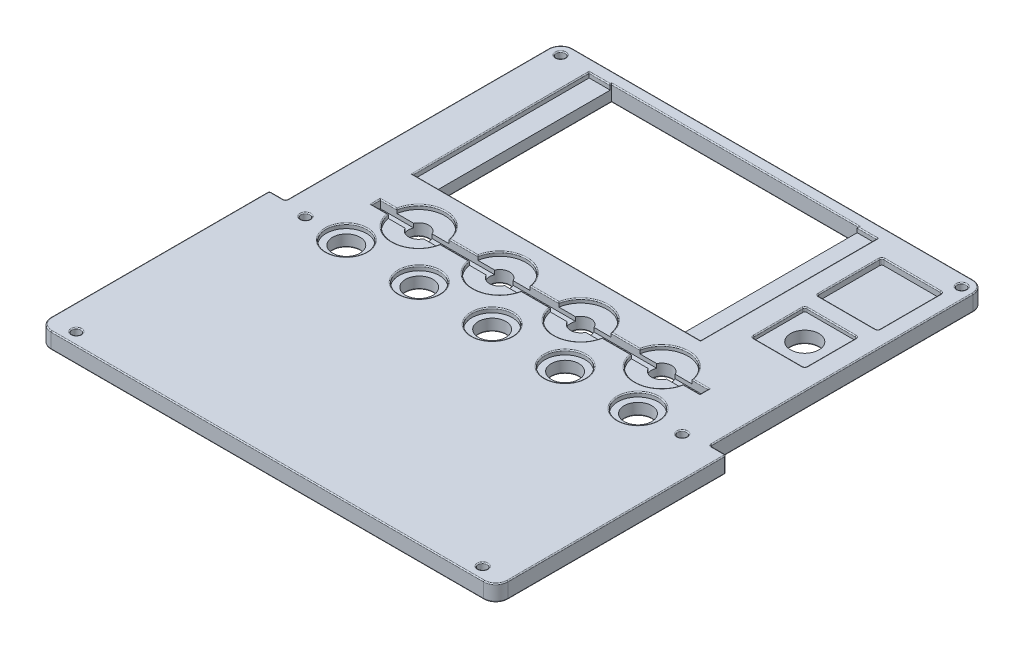
SolidWorks part; units mm, degrees
ref_plane "Front Plane" through (0, 0, 0) normal (0, 0, 1) x (1, 0, 0)
ref_plane "Top Plane" through (0, 0, 0) normal (0, 1, 0) x (1, 0, 0)
ref_plane "Right Plane" through (0, 0, 0) normal (1, 0, 0) x (0, 0, -1)
sketch "Sketch1" plane through (0, 0, 0) normal (0, 1, 0) x (1, 0, 0)
  line L0 (112.8, 56.9) -> (108.8, 56.9)
  line L1 (0, 0) -> (112.8, 0)
  line L2 (0, 0) -> (0, 56.9)
  line L3 (0, 56.9) -> (112.8, 56.9) construction
  line L4 (112.8, 0) -> (112.8, 56.9)
  line L5 (4, 56.9) -> (0, 56.9)
  line L6 (4, 56.9) -> (4, 124.8)
  line L7 (4, 124.8) -> (108.8, 124.8)
  line L8 (108.8, 56.9) -> (108.8, 124.8)
  line L9 (0, 56.9) -> (112.8, 56.9) construction
  dimension "D1" = 104.8
  dimension "D2" = 112.8
  dimension "D3" = 67.9
  dimension "D4" = 56.9
extrude "Main" add sketch "Sketch1" along normal blind 4
sketch "Outline Display" plane through (0, 0, 0) normal (0, -1, 0) x (1, 0, 0)
  line L0 (4, -124.8) -> (4, -81.05) construction
  line L1 (4, -124.8) -> (4, -56.9) construction
  line L2 (4, -81.05) -> (17, -81.05) construction
  line L3 (17, -81.05) -> (17, -78.32) construction
  line L4 (14.23, -78.32) -> (85.03, -78.32) construction
  line L5 (14.23, -78.32) -> (14.23, -121.62) construction
  line L6 (14.23, -121.62) -> (85.03, -121.62) construction
  line L7 (85.03, -78.32) -> (85.03, -121.62) construction
  line L8 (17, -81.05) -> (14.23, -81.05) construction
  point P7 (17, -81.05)
  dimension "D1" = 43.75
  dimension "D2" = 13
  dimension "D3" = 2.73
  dimension "D4" = 2.77
  dimension "D5" = 43.3
  dimension "D6" = 70.8
sketch "Display PCB Notch" plane through (0, 4, 0) normal (0, -1, 0) x (1, 0, 0)
  line L0 (14.23, -78.32) -> (14.23, -78.22) construction
  line L1 (14.13, -78.22) -> (85.13, -78.22)
  line L2 (14.13, -78.22) -> (14.13, -121.72)
  line L3 (14.13, -121.72) -> (85.13, -121.72)
  line L4 (85.13, -78.22) -> (85.13, -121.72)
  line L5 (14.23, -78.32) -> (14.13, -78.32) construction
  line L6 (85.03, -121.62) -> (85.03, -121.72) construction
  line L7 (85.03, -121.62) -> (85.13, -121.62) construction
  dimension "D2" = 0.1
extrude "PCB Notch" cut sketch "Display PCB Notch" along normal blind 1.2
sketch "Sketch4" plane through (0, 0, 0) normal (0, -1, 0) x (-1, 0, 0)
  line L0 (-14.23, 78.32) -> (-85.03, 78.32) construction
  line L1 (-19.33, 78.87) -> (-80.29, 78.87)
  line L2 (-19.33, 78.87) -> (-19.33, 122.05)
  line L3 (-19.33, 122.05) -> (-80.29, 122.05)
  line L4 (-80.29, 78.87) -> (-80.29, 122.05)
  dimension "D1" = 5.1
  dimension "D2" = 0.55
  dimension "D3" = 60.96
  dimension "D4" = 43.18
extrude "Display Cut" cut sketch "Sketch4" against normal up to next
sketch "Sketch5" plane through (0, 0, 0) normal (0, -1, 0) x (1, 0, 0)
  line L0 (108.8, -56.9) -> (108.8, -124.8) construction
  line L1 (89.12, -102.2) -> (97.32, -102.2) construction
  line L2 (97.32, -102.2) -> (97.32, -91.75) construction
  circle A0 centre (97.32, -91.75) radius 3.5
  point P0 (89.12, -102.2)
  point P1 (108.8, -124.8)
  point P9 (97.32, -91.75)
  dimension "D5" = 7
  dimension "D1" = 22.6
  dimension "D2" = 19.68
  dimension "D3" = 10.45
  dimension "D4" = 8.2
extrude "Rotary Hole" cut sketch "Sketch5" against normal up to next
sketch "Sketch6" plane through (0, 0, 0) normal (0, -1, 0) x (1, 0, 0)
  line L0 (6.9, -124.8) -> (6.9, -121.9) construction
  line L1 (108.8, -124.8) -> (4, -124.8) construction
  line L2 (6.9, -121.9) -> (4, -121.9) construction
  line L3 (4, -124.8) -> (4, -56.9) construction
  line L4 (56.4, 0) -> (56.4, -124.8) construction
  line L5 (0, 0) -> (112.8, 0) construction
  line L6 (0, -55.9) -> (9.9, -55.9) construction
  line L7 (0, -56.9) -> (0, 0) construction
  line L8 (4, -56.9) -> (0, -56.9) construction
  line L9 (0, -3) -> (6.25, -3) construction
  circle A0 centre (6.9, -121.9) radius 1.1
  circle A1 centre (9.9, -55.9) radius 1.1
  circle A2 centre (6.25, -3) radius 1.1
  circle A3 centre (105.9, -121.9) radius 1.1
  circle A4 centre (102.9, -55.9) radius 1.1
  circle A5 centre (106.55, -3) radius 1.1
  dimension "D1" = 2.2
  dimension "D7" = 6.25
  dimension "D2" = 2.9
  dimension "D3" = 2.9
  dimension "D4" = 9.9
  dimension "D5" = 1
  dimension "D6" = 3
extrude "Mounts" cut sketch "Sketch6" against normal up to next contours A0 | A1 | A2 | A5 | A4 | A3
fillet "Fillet1" radius 3 4 edges at (112.8, 2, 0) (108.8, 2, -124.8) (4, 2, -124.8) (0, 2, 0)
sketch "Sketch7" plane through (0, 0, 0) normal (0, -1, 0) x (1, 0, 0)
  line L0 (17, -81.05) -> (17, -75.8) construction
  line L1 (17, -59.7) -> (4, -59.7) construction
  line L2 (17, -75.8) -> (95.8, -75.8)
  line L3 (17, -75.8) -> (17, -59.7)
  line L4 (17, -59.7) -> (95.8, -59.7)
  line L5 (95.8, -75.8) -> (95.8, -59.7)
  line L6 (4, -121.8) -> (4, -56.9) construction
  line L7 (95.8, -59.7) -> (108.8, -59.7) construction
  line L8 (108.8, -56.9) -> (108.8, -121.8) construction
  line L9 (17, -67.75) -> (95.8, -67.75) construction
  circle A0 centre (26, -67.75) radius 2.5
  circle A1 centre (46, -67.75) radius 2.5
  circle A2 centre (66, -67.75) radius 2.5
  circle A3 centre (86, -67.75) radius 2.5
  dimension "D3" = 5
  dimension "D1" = 5.25
  dimension "D2" = 16.1
  dimension "D4" = 9
  dimension "D5" = 20
  dimension "D6" = 20
  dimension "D7" = 20
extrude "Toggle Mounts" cut sketch "Sketch7" against normal up to next contours A0 | A1 | A2 | A3 region at (26, 0, -67.75) region at (46, 0, -67.75) region at (66, 0, -67.75) region at (86, 0, -67.75)
sketch "Sketch8" plane through (0, 4, 0) normal (0, -1, 0) x (1, 0, 0)
  line L0 (88.5, -67.75) -> (23.5, -67.75) construction
  line L1 (96.5, -67.75) -> (88.5, -67.75) construction
  line L2 (96.5, -68.8) -> (15.5, -68.8)
  line L3 (96.5, -68.8) -> (96.5, -66.7)
  line L4 (96.5, -66.7) -> (15.5, -66.7)
  line L5 (15.5, -68.8) -> (15.5, -66.7)
  line L6 (23.5, -67.75) -> (15.5, -67.75) construction
  line L7 (23.5, -67.75) -> (23.5, -68.8) construction
  line L8 (23.5, -67.75) -> (23.5, -66.7) construction
  circle A0 centre (86, -67.75) radius 2.5 construction
  circle A1 centre (26, -67.75) radius 2.5 construction
  circle A2 centre (86, -67.75) radius 2.5 construction
  circle A3 centre (86, -67.75) radius 2.5 construction
  circle A4 centre (26, -67.75) radius 2.5 construction
  circle A5 centre (26, -67.75) radius 2.5 construction
  dimension "D1" = 8
  dimension "D2" = 2.1
extrude "Toggle Direction" cut sketch "Sketch8" along normal blind 2
sketch "Sketch9" plane through (0, 4, 0) normal (0, 1, 0) x (1, 0, 0)
  circle A0 centre (26, 67.75) radius 6.5
  circle A1 centre (46, 67.75) radius 6.5
  circle A2 centre (66, 67.75) radius 6.5
  circle A3 centre (86, 67.75) radius 6.5
  point P0 (26, 67.75)
  point P1 (46, 67.75)
  point P3 (66, 67.75)
  point P5 (86, 67.75)
  dimension "D1" = 13
extrude "Toggle Countersinks" cut sketch "Sketch9" against normal blind 1
sketch "Sketch10" plane through (0, 4, 0) normal (0, 1, 0) x (1, 0, 0)
  line L1 (90.82, 98.25) -> (103.82, 98.25)
  line L2 (90.82, 98.25) -> (90.82, 85.25)
  line L3 (90.82, 85.25) -> (103.82, 85.25)
  line L4 (103.82, 98.25) -> (103.82, 85.25)
  line L5 (90.82, 98.25) -> (103.82, 85.25) construction
  line L6 (90.82, 85.25) -> (103.82, 98.25) construction
  point P0 (97.32, 91.75)
  point P1 (97.32, 91.75)
  dimension "D1" = 13
extrude "Encoder Clearance" cut sketch "Sketch10" against normal blind 1
sketch "Sketch11" plane through (0, 4, 0) normal (0, 1, 0) x (1, 0, 0)
  line L1 (89.82, 102.25) -> (104.82, 102.25)
  line L2 (89.82, 102.25) -> (89.82, 118.25)
  line L3 (89.82, 118.25) -> (104.82, 118.25)
  line L4 (104.82, 102.25) -> (104.82, 118.25)
  line L5 (89.82, 102.25) -> (104.82, 118.25) construction
  line L6 (89.82, 118.25) -> (104.82, 102.25) construction
  line L10 (103.82, 85.25) -> (103.82, 98.25)
  line L11 (103.82, 98.25) -> (90.82, 98.25)
  line L12 (90.82, 98.25) -> (90.82, 85.25)
  line L13 (90.82, 85.25) -> (103.82, 85.25)
  line L14 (103.82, 85.25) -> (103.82, 98.25) construction
  line L15 (103.82, 98.25) -> (90.82, 98.25) construction
  line L16 (90.82, 98.25) -> (90.82, 85.25) construction
  line L17 (90.82, 85.25) -> (103.82, 85.25) construction
  point P4 (97.32, 110.25)
  dimension "D2" = 1
  dimension "D3" = 1
  dimension "D4" = 4
  dimension "D5" = 16
  dimension "D1" = 0
extrude "Encoder Pin Clearance" cut sketch "Sketch11" against normal blind 1.5
fillet "Fillet2" radius 0.5 12 edges at (0, 2, -56.9) (4, 2, -56.9) (112.8, 2, -56.9) (108.8, 2, -56.9) (89.82, 3.25, -102.25) (89.82, 3.25, -118.25) (104.82, 3.25, -118.25) (104.82, 3.25, -102.25) (103.82, 3.5, -85.25) (103.82, 3.5, -98.25) (90.82, 3.5, -98.25) (90.82, 3.5, -85.25)
sketch "Sketch12" plane through (0, 4, 0) normal (0, 1, 0) x (1, 0, 0)
  line L0 (9.9, 55.9) -> (102.9, 55.9) construction
  line L1 (38, 66.7) -> (38, 59.3) construction
  line L3 (56, 66.7) -> (56, 59.3) construction
  line L4 (59.5854, 66.7) -> (52.4146, 66.7) construction
  line L5 (74, 66.7) -> (74, 59.3) construction
  line L7 (38, 59.3) -> (20, 59.3) construction
  line L8 (38, 59.3) -> (56, 59.3) construction
  line L9 (74, 59.3) -> (92, 59.3) construction
  line L10 (56, 59.3) -> (74, 59.3) construction
  circle A2 centre (20, 55.9) radius 3.4
  circle A3 centre (38, 55.9) radius 3.4
  circle A4 centre (56, 55.9) radius 3.4
  circle A5 centre (74, 55.9) radius 3.4
  circle A6 centre (92, 55.9) radius 3.4
  point P3 (9.9, 55.9)
  point P4 (102.9, 55.9)
  dimension "D1" = 6.8
  dimension "D2" = 18
extrude "LED Mounts" cut sketch "Sketch12" against normal up to next
sketch "Sketch13" plane through (0, 4, 0) normal (0, 1, 0) x (1, 0, 0)
  circle A0 centre (20, 55.9) radius 5
  circle A1 centre (38, 55.9) radius 5
  circle A2 centre (56, 55.9) radius 5
  circle A3 centre (74, 55.9) radius 5
  circle A4 centre (92, 55.9) radius 5
  point P0 (20, 55.9)
  point P1 (38, 55.9)
  point P3 (56, 55.9)
  point P5 (74, 55.9)
  point P7 (92, 55.9)
  dimension "D1" = 10
extrude "LED Countersink" cut sketch "Sketch13" against normal blind 1.1
fillet "Fillet4" radius 0.25 107 edges at (4, 4, -89.6) (4.8787, 4, -123.9213) (56.4, 4, -124.8) (111.9213, 4, -0.8787) (56.4, 4, 0) (4, 0, -89.6) (4.8787, 0, -123.9213) (56.4, 0, -124.8) (112.8, 0, -29.7) (111.9213, 0, -0.8787) (56.4, 0, 0) (108.9464, 4, -57.0464) (108.9464, 0, -57.0464) (3.8536, 4, -57.0464) (3.8536, 0, -57.0464) (90.9664, 4, -85.3964) (90.9664, 4, -98.1036) (103.6736, 4, -98.1036) (103.6736, 4, -85.3964) (104.6736, 4, -102.3964) (104.6736, 4, -118.1036) (89.9664, 4, -118.1036) (89.9664, 4, -102.3964) (0.1464, 4, -56.7536) (112.6536, 4, -56.7536) (0.1464, 0, -56.7536) (112.6536, 0, -56.7536) (107.9213, 4, -123.9213) (0.8787, 4, -0.8787) (107.9213, 0, -123.9213) (0.8787, 0, -0.8787) (2, 4, -56.9) (108.8, 4, -89.6) (110.8, 4, -56.9) (112.8, 4, -29.7) (0, 4, -29.7) (2, 0, -56.9) (108.8, 0, -89.6) (110.8, 0, -56.9) (0, 0, -29.7) (49.63, 4, -78.22) (85.13, 4, -99.97) (82.71, 4, -121.72) (16.73, 4, -121.72) (14.13, 4, -99.97) (49.81, 0, -78.87) (80.29, 0, -100.46) (49.81, 0, -122.05) (19.33, 0, -100.46) (97.32, 0, -95.25) (9.9, 4, -54.8) (9.9, 0, -57) (6.25, 4, -1.9) (6.25, 0, -4.1) (106.55, 0, -1.9) (106.55, 4, -1.9) (102.9, 0, -54.8) (102.9, 4, -54.8) (105.9, 0, -120.8) (105.9, 4, -120.8) (26, 0, -70.25) (46, 0, -70.25) (66, 0, -70.25) (86, 0, -70.25) (17.5427, 4, -68.8) (36, 4, -68.8) (56, 4, -68.8) (76, 4, -68.8) (94.4573, 4, -68.8) (15.5, 4, -67.75) (94.4573, 4, -66.7) (76, 4, -66.7) (56, 4, -66.7) (36, 4, -66.7) (17.5427, 4, -66.7) (96.5, 4, -67.75) (26, 4, -74.25) (26, 4, -61.25) (46, 4, -74.25) (46, 4, -61.25) (66, 4, -74.25) (66, 4, -61.25) (86, 4, -74.25) (86, 4, -61.25) (97.32, 4, -85.25) (90.82, 4, -91.75) (97.32, 4, -98.25) (103.82, 4, -91.75) (97.32, 4, -118.25) (104.82, 4, -110.25) (97.32, 4, -102.25) (89.82, 4, -110.25) (92, 0, -52.5) (20, 0, -52.5) (38, 0, -52.5) (56, 0, -52.5) (74, 0, -52.5) (20, 4, -50.9) (38, 4, -50.9) (56, 4, -50.9) (74, 4, -50.9) (92, 4, -50.9) (6.9, 4, -120.8) (80.29, 4, -121.885) (49.81, 4, -122.05) (19.33, 4, -121.885) (6.9, 0, -123)
